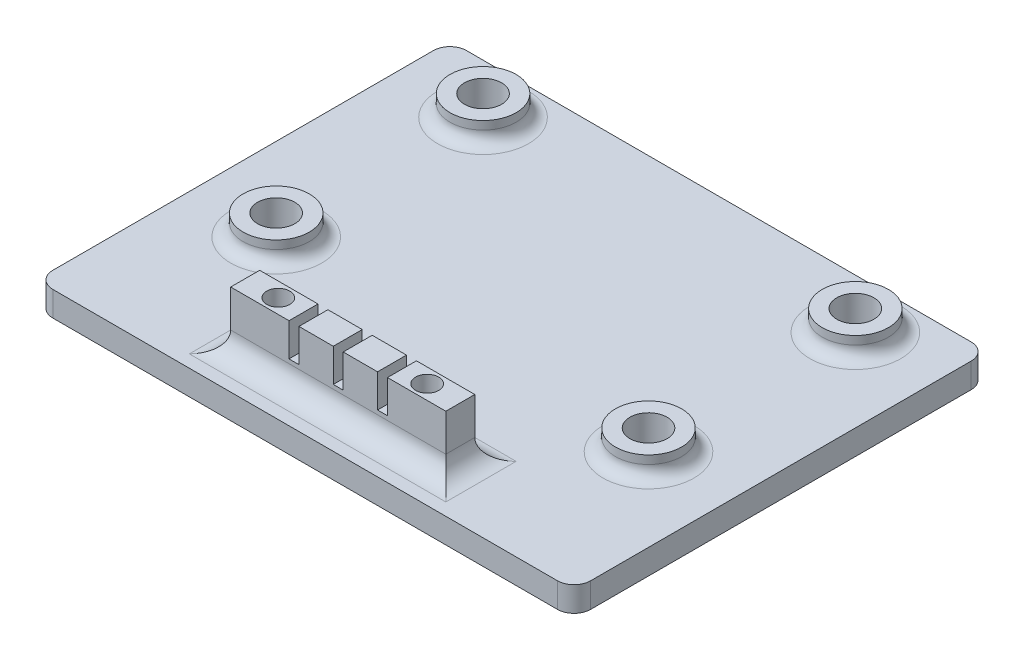
SolidWorks part; units mm, degrees
ref_plane "Ebene vorne" through (0, 0, 0) normal (0, 0, 1) x (1, 0, 0)
ref_plane "Ebene oben" through (0, 0, 0) normal (0, 1, 0) x (1, 0, 0)
ref_plane "Ebene rechts" through (0, 0, 0) normal (1, 0, 0) x (0, 0, -1)
sketch "Skizze1" plane through (0, 0, 0) normal (0, 1, 0) x (1, 0, 0)
  line L1 (-32.5, 0) -> (32.5, 0)
  line L2 (-32.5, 0) -> (-32.5, 50)
  line L3 (-32.5, 50) -> (32.5, 50)
  line L4 (32.5, 0) -> (32.5, 50)
  point P4 (0, 0)
  dimension "D1" = 65
  dimension "D2" = 50
extrude "Aufsatz-Linear austragen1" add sketch "Skizze1" along normal blind 3
fillet "Verrundung1" radius 2 4 edges at (-32.5, 1.5, -50) (32.5, 1.5, -50) (32.5, 1.5, 0) (-32.5, 1.5, 0)
sketch "Skizze10" plane through (0, 3, 0) normal (0, 1, 0) x (1, 0, 0)
  line L0 (30.5, 50) -> (-30.5, 50) construction
  line L1 (-22.5, 44) -> (22.5, 44) construction
  line L2 (-22.5, 44) -> (-22.5, 19) construction
  line L3 (-22.5, 19) -> (22.5, 19) construction
  line L4 (22.5, 44) -> (22.5, 19) construction
  circle A0 centre (-22.5, 44) radius 4
  circle A1 centre (-22.5, 19) radius 4
  circle A2 centre (22.5, 44) radius 4
  circle A3 centre (22.5, 19) radius 4
  point P2 (0, 19)
  dimension "D1" = 8
  dimension "D2" = 45
  dimension "D3" = 25
  dimension "D4" = 6
extrude "Aufsatz-Linear austragen4" add sketch "Skizze10" along normal blind 2.5
hole_wizard "Stirnsenkung für M3 Senkschraube (Kopf Button)5" positions "Skizze2" profile "Skizze3" counterbore size "M3" standard "ANSI Metrisch" end condition through all
sketch "Skizze2" plane through (0, 0, 0) normal (0, 1, 0) x (1, 0, 0)
  line L1 (-22.5, 19) -> (22.5, 19)
  line L2 (-22.5, 19) -> (-22.5, 44)
  line L3 (-22.5, 44) -> (22.5, 44)
  line L4 (22.5, 19) -> (22.5, 44)
  line L5 (30.5, 50) -> (-30.5, 50) construction
  point P0 (-22.5, 19)
  point P1 (22.5, 44)
  point P74 (-22.5, 44)
  point P75 (22.5, 19)
  point P77 (0, 19)
  dimension "D1" = 45
  dimension "D2" = 25
  dimension "D3" = 6
sketch "Skizze3" plane through (-22.5, 0, -19) normal (1, 0, 0) x (0, 0, -1)
  line L0 (0, 0) -> (0, 5.5)
  line L1 (0, 5.5) -> (2.25, 5.5)
  line L3 (2.25, 5.5) -> (2.25, 0.3)
  line L4 (2.25, 0.3) -> (2.45, 0.3)
  line L5 (2.45, 0.3) -> (2.45, 0)
  line L7 (2.45, 0) -> (0, 0)
  line L11 (0, -6.35) -> (0, 107.95) construction
  dimension "Bohrerdurchmesser" = 4.5
  dimension "Bohrungstiefe" = 5.5
  dimension "Senkdurchmesser2" = 4.9
  dimension "Senktiefe2" = 0.3
sketch "Skizze9" plane through (0, 3, 0) normal (0, 1, 0) x (1, 0, 0)
  line L0 (-30.5, 0) -> (30.5, 0) construction
  line L1 (-20, 20) -> (20, 20)
  line L2 (-20, 20) -> (-20, 0)
  line L4 (20, 20) -> (20, 0)
  point P4 (0, 20)
  dimension "D1" = 20
  dimension "D2" = 40
sketch "Skizze8" plane through (0, 0, 0) normal (1, 0, 0) x (0, 0, -1)
  line L0 (4, 3) -> (4, 10)
  line L1 (2, 3) -> (48, 3) construction
  line L2 (4, 10) -> (7.5, 10)
  line L3 (7.5, 10) -> (7.5, 3)
  line L4 (7.5, 3) -> (4, 3)
  line L6 (20, 3) -> (0, 3) construction
  dimension "D1" = 90
  dimension "D2" = 7
  dimension "D3" = 3.5
  dimension "D4" = 4
extrude "Aufsatz-Linear austragen3" add sketch "Skizze8" along normal mid plane 26
sketch "Skizze4" plane through (0, 3, 0) normal (0, 1, 0) x (1, 0, 0)
  line L1 (-13, 13.8) -> (13, 13.8)
  line L2 (-13, 13.8) -> (-13, 10)
  line L3 (-13, 10) -> (13, 10)
  line L4 (13, 13.8) -> (13, 10)
  point P4 (0, 10)
  dimension "D1" = 10
  dimension "D2" = 3.8
  dimension "D3" = 26
ref_plane "Ebene1" through (0, -5, 0) normal (0, 1, 0) x (1, 0, 0)
hole_wizard "Stirnsenkung für M3 Senkschraube (Kopf Button)4" positions "Skizze5" profile "Skizze6" counterbore size "M3" standard "ANSI Metrisch" end condition through all
sketch "Skizze5" plane through (0, -5, 1.9177) normal (0, -1, 0) x (-1, 0, 0)
  line L0 (9, 7.6677) -> (-9, 7.6677)
  line L2 (0, 5.9177) -> (0, 9.4177) construction
  point P0 (9, 7.6677)
  point P2 (-9, 7.6677)
  point P8 (0, 7.6677)
  point P12 (0, 7.6677)
  dimension "D1" = 18
sketch "Skizze6" plane through (-9, -5, -5.75) normal (1, 0, 0) x (0, 0, -1)
  line L0 (0, 0) -> (0, 15)
  line L1 (0, 15) -> (1.4, 15)
  line L3 (1.4, 15) -> (1.4, 6)
  line L4 (1.4, 6) -> (3, 6)
  line L5 (3, 6) -> (3, 0)
  line L7 (3, 0) -> (0, 0)
  line L11 (0, -6.35) -> (0, 107.95) construction
  dimension "Bohrerdurchmesser" = 2.8
  dimension "Bohrungstiefe" = 15
  dimension "Senkdurchmesser2" = 6
  dimension "Senktiefe2" = 6
sketch "Skizze7" plane through (0, 10, 0) normal (0, 1, 0) x (1, 0, 0)
  line L6 (0.6, 7.5) -> (0.6, 4)
  line L11 (-5.95, 7.5) -> (-4.75, 7.5)
  line L12 (-5.95, 7.5) -> (-5.95, 4)
  line L13 (-5.95, 4) -> (-4.75, 4)
  line L14 (-4.75, 7.5) -> (-4.75, 4)
  line L15 (-0.6, 4) -> (0.6, 4)
  line L16 (-0.6, 7.5) -> (-0.6, 4)
  line L17 (-0.6, 7.5) -> (0.6, 7.5)
  line L18 (5.95, 7.5) -> (5.95, 4)
  line L19 (4.75, 4) -> (5.95, 4)
  line L20 (4.75, 7.5) -> (4.75, 4)
  line L21 (4.75, 7.5) -> (5.95, 7.5)
  line L22 (13, 4) -> (-13, 4) construction
  line L23 (13, 7.5) -> (-13, 7.5) construction
  point P0 (-5.35, 4)
  dimension "D1" = 5.35
  dimension "D2" = 1.2
  dimension "D3" = 3
extrude "Schnitt-Linear austragen1" cut sketch "Skizze7" against normal blind 4
fillet "Verrundung2" radius 1.5 4 edges at (-22.5, 3, -48) (-22.5, 3, -23) (22.5, 3, -48) (22.5, 3, -23)
fillet "Verrundung5" radius 2.5 3 edges at (-13, 3, -5.75) (13, 3, -5.75) (0, 3, -4)
fillet "Verrundung6" radius 2.5 1 edges at (0, 3, -7.5)
